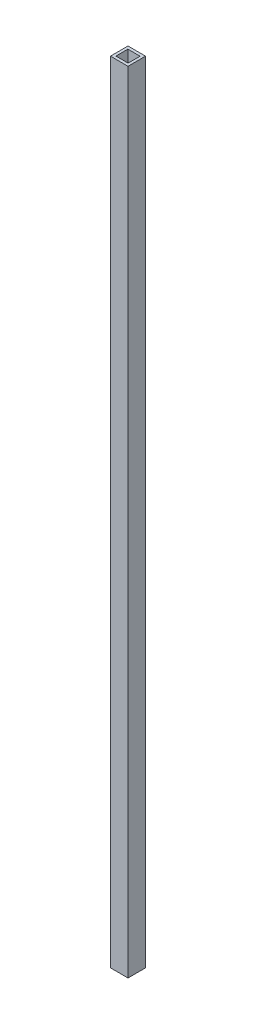
SolidWorks part; units mm, degrees
ref_plane "Front Plane" through (0, 0, 0) normal (0, 0, 1) x (1, 0, 0)
ref_plane "Top Plane" through (0, 0, 0) normal (0, 1, 0) x (1, 0, 0)
ref_plane "Right Plane" through (0, 0, 0) normal (1, 0, 0) x (0, 0, -1)
sketch "Sketch1" plane through (0, 0, 0) normal (0, 1, 0) x (1, 0, 0)
  line L1 (-12.7, 12.7) -> (12.7, 12.7)
  line L2 (-12.7, 12.7) -> (-12.7, -12.7)
  line L3 (-12.7, -12.7) -> (12.7, -12.7)
  line L4 (12.7, 12.7) -> (12.7, -12.7)
  line L5 (-12.7, 12.7) -> (12.7, -12.7) construction
  line L6 (-12.7, -12.7) -> (12.7, 12.7) construction
  point P0 (0, 0)
extrude "Boss-Extrude1" add sketch "Sketch1" along normal blind 1143
sketch "Sketch2" plane through (0, 0, 0) normal (0, -1, 0) x (1, 0, 0)
  line L1 (-8.8378, 8.6745) -> (8.8378, 8.6745)
  line L2 (-8.8378, 8.6745) -> (-8.8378, -8.6745)
  line L3 (-8.8378, -8.6745) -> (8.8378, -8.6745)
  line L4 (8.8378, 8.6745) -> (8.8378, -8.6745)
  line L5 (-8.8378, 8.6745) -> (8.8378, -8.6745) construction
  line L6 (-8.8378, -8.6745) -> (8.8378, 8.6745) construction
  point P0 (0, 0)
extrude "Cut-Extrude1" cut sketch "Sketch2" against normal blind 1143
